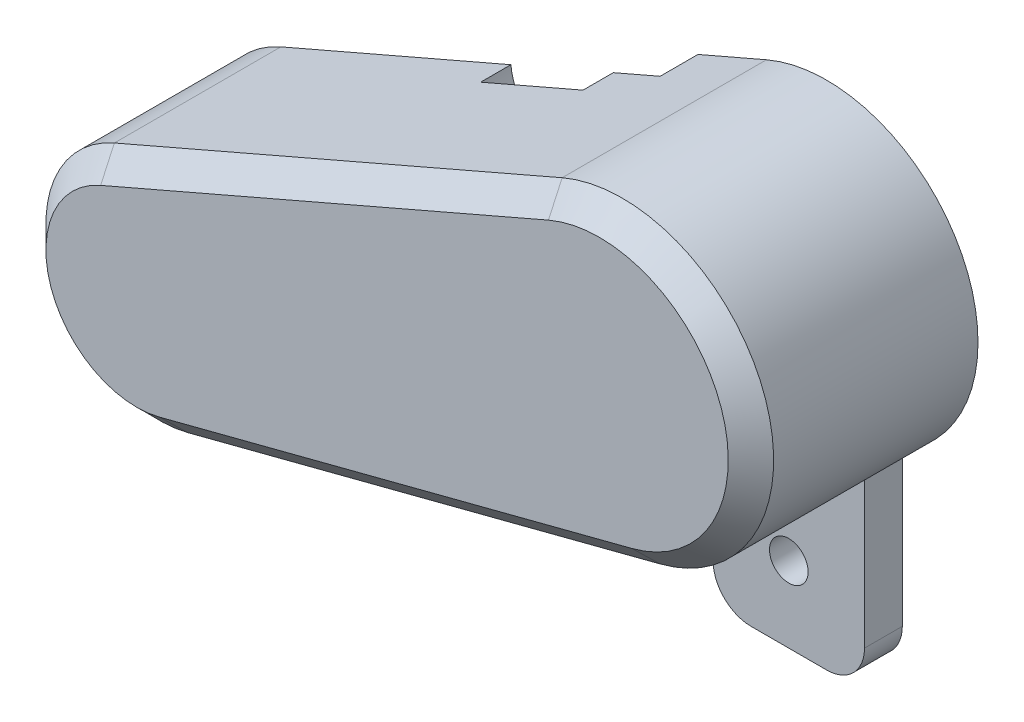
SolidWorks part; units mm, degrees
material "ABS"
ref_plane "Front Plane" through (0, 0, 0) normal (0, 0, 1) x (1, 0, 0)
ref_plane "Top Plane" through (0, 0, 0) normal (0, 1, 0) x (1, 0, 0)
ref_plane "Right Plane" through (0, 0, 0) normal (1, 0, 0) x (0, 0, -1)
sketch "Sketch1" plane through (0, 0, 0) normal (0, 0, 1) x (1, 0, 0)
  circle A1 centre (19, -32.5) radius 12.435
  circle A3 centre (-42.15, -53.5167) radius 7.5
ref_plane "Plane1" through (0, 0, 22) normal (0, 0, 1) x (1, 0, 0)
ref_plane "Plane2" through (0, 0, 27) normal (0, 0, 1) x (1, 0, 0)
sketch "Sketch2" plane through (0, 0, 27) normal (0, 0, 1) x (1, 0, 0)
  line L0 (-48.1078, -39.7506) -> (11.0563, -14.1452)
  line L1 (-38.3861, -68.0367) -> (24.0186, -51.8601)
  arc A0 (24.0186, -51.8601) -> (11.0563, -14.1452) centre (19, -32.5) ccw
  arc A1 (-48.1078, -39.7506) -> (-38.3861, -68.0367) centre (-42.15, -53.5167) ccw
  dimension "D1" = 40
  dimension "D2" = 30
extrude "Boss-Extrude1" add sketch "Sketch2" along normal blind 3
sketch "Sketch3" plane through (0, 0, 27) normal (0, 0, -1) x (-1, 0, 0)
  line L0 (46.9162, -42.5038) -> (-12.2479, -16.8984)
  line L1 (-23.2658, -48.9561) -> (39.1389, -65.1327)
  line L2 (48.1078, -39.7506) -> (-11.0563, -14.1452)
  line L3 (-24.0186, -51.8601) -> (38.3861, -68.0367)
  line L4 (48.1078, -39.7506) -> (-11.0563, -14.1452)
  line L5 (-24.0186, -51.8601) -> (38.3861, -68.0367)
  arc A0 (39.1389, -65.1327) -> (46.9162, -42.5038) centre (42.15, -53.5167) ccw
  arc A1 (-12.2479, -16.8984) -> (-23.2658, -48.9561) centre (-19, -32.5) ccw
  arc A2 (38.3861, -68.0367) -> (48.1078, -39.7506) centre (42.15, -53.5167) ccw
  arc A3 (-11.0563, -14.1452) -> (-24.0186, -51.8601) centre (-19, -32.5) ccw
  arc A4 (38.3861, -68.0367) -> (48.1078, -39.7506) centre (42.15, -53.5167) ccw
  arc A5 (-11.0563, -14.1452) -> (-24.0186, -51.8601) centre (-19, -32.5) ccw
  dimension "D1" = 0
  dimension "D2" = 3
extrude "Boss-Extrude2" add sketch "Sketch3" along normal up to surface (27 mm away) up to plane "Front Plane"
chamfer "Chamfer1" distance 3 angle 45 8 edges at (-7.9365, -57.0444, 27) (-53.4984, -57.417, 27) (35.077, -26.9745, 27) (-17.3342, -29.7011, 27) (-7.1838, -59.9484, 30) (37.9141, -25.9994, 30) (-56.3356, -58.3921, 30) (-18.5257, -26.9479, 30)
ref_plane "Plane3" through (0, 0, 5) normal (0, 0, 1) x (1, 0, 0)
sketch "Sketch4" plane through (0, 0, 5) normal (0, 0, 1) x (1, 0, 0)
  line L1 (-20, -37.3667) -> (-20, -69.6667) construction
  line L3 (0, -12.5) -> (0, -37.3667) construction
  line L5 (425, -10) -> (0, -10) construction
  line L7 (425, 10) -> (0, 10) construction
  line L8 (-20, -37.3667) -> (0, -37.3667) construction
  line L9 (-20, -69.6667) -> (-61.6761, -69.6667) construction
  line L10 (-61.6761, -69.6667) -> (-61.6761, -12.5) construction
  line L11 (-61.6761, -12.5) -> (0, -12.5) construction
  line L12 (-63.6761, -10.5) -> (2, -10.5)
  line L13 (2, -10.5) -> (2, -39.3667)
  line L14 (-18, -39.3667) -> (2, -39.3667)
  line L15 (-18, -39.3667) -> (-18, -71.6667)
  line L16 (-18, -71.6667) -> (-63.6761, -71.6667)
  line L17 (-63.6761, -71.6667) -> (-63.6761, -10.5)
  circle A1 centre (-10, -25.8667) radius 4.75 construction
  circle A2 centre (-10, -25.8667) radius 7.75
  dimension "D1" = 2
  dimension "D2" = 3
extrude "Cut-Extrude1" cut sketch "Sketch4" against normal up to surface (5 mm away) contours L12 L13 L14 L15 L16 L17 up to face at (-10.9231, -42.7843, 0)
extrude "Cut-Extrude2" cut sketch "Sketch4<3>" along normal blind 4 contours A2
sketch "Sketch4<3>" plane through (0, 0, 5) normal (0, 0, 1) x (1, 0, 0) same geometry as "Sketch4"
sketch "Sketch5" plane through (0, 0, 0) normal (0, 0, -1) x (-1, 0, 0)
  line L0 (-9, -15.0352) -> (-9, 5)
  line L1 (-14, 10) -> (-24, 10)
  line L2 (-29, 5) -> (-29, -15.1795)
  line L3 (-19, 10) -> (-19, -32.5) construction
  line L5 (-11.0563, -14.1452) -> (-9, -15.0352)
  arc A1 (-11.0563, -14.1452) -> (-29, -15.1795) centre (-19, -32.5) ccw
  circle A2 centre (-19, 0) radius 2.75
  arc A3 (-24, 10) -> (-29, 5) centre (-24, 5) ccw
  arc A4 (-14, 10) -> (-9, 5) centre (-14, 5) cw
  point P13 (-29, 10)
  point P16 (-9, 10)
  dimension "D2" = 10
  dimension "D3" = 5
  dimension "D4" = 5.5
  dimension "D1" = 20
extrude "Boss-Extrude3" [suppressed] add sketch "Sketch5" against normal blind 5
sketch "Sketch7" plane through (0, 0, 0) normal (0, 0, -1) x (-1, 0, 0)
  line L0 (-9, -55.7533) -> (-9, -70)
  line L1 (-14, -75) -> (-24, -75)
  line L2 (-29, -70) -> (-29, -49.8205)
  line L3 (18, -62.7522) -> (-24.0186, -51.8601) construction
  line L4 (-9, -55.7533) -> (-24.0186, -51.8601)
  line L5 (-19, -32.5) -> (-19, -75) construction
  arc A0 (-11.0563, -14.1452) -> (-24.0186, -51.8601) centre (-19, -32.5) ccw construction
  arc A1 (-29, -49.8205) -> (-24.0186, -51.8601) centre (-19, -32.5) ccw
  arc A2 (-29, -70) -> (-24, -75) centre (-24, -70) ccw
  arc A3 (-14, -75) -> (-9, -70) centre (-14, -70) ccw
  circle A4 centre (-19, -65) radius 2.55
  circle A5 centre (-19, -32.5) radius 12.435 construction
  point P0 (-19, -75)
  point P12 (-29, -75)
  point P15 (-9, -75)
  dimension "D2" = 5
  dimension "D3" = 10
  dimension "D4" = 32.5
  dimension "D5" = 5.1
  dimension "D1" = 20
extrude "Boss-Extrude5" add sketch "Sketch7" against normal blind 5
